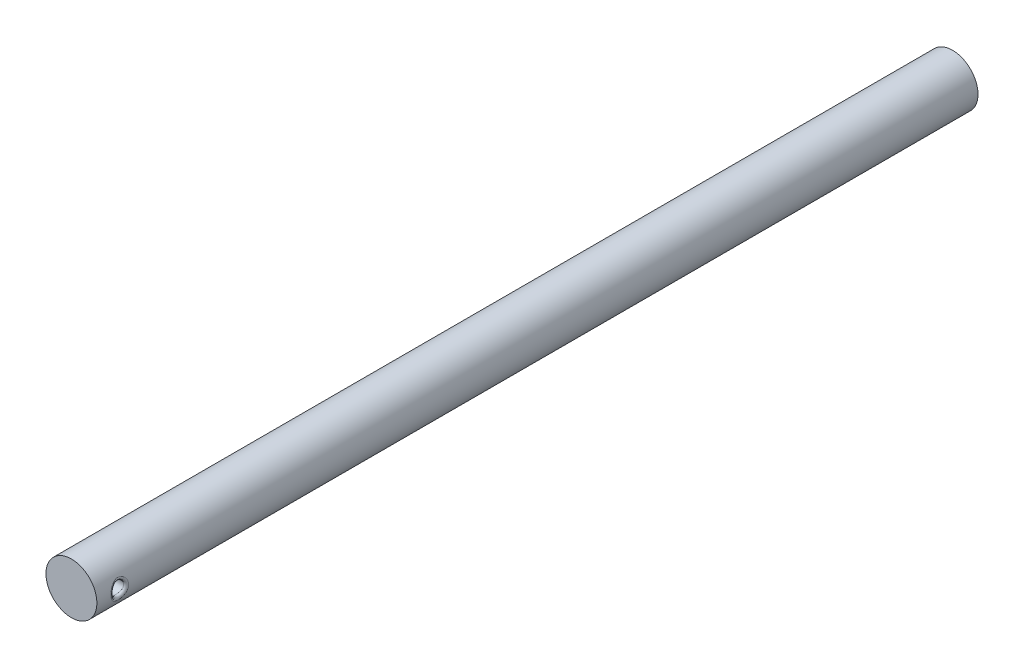
SolidWorks part; units mm, degrees
ref_plane "Alzado" through (0, 0, 0) normal (0, 0, 1) x (1, 0, 0)
ref_plane "Planta" through (0, 0, 0) normal (0, 1, 0) x (1, 0, 0)
ref_plane "Vista lateral" through (0, 0, 0) normal (1, 0, 0) x (0, 0, -1)
sketch "Croquis1" plane through (0, 0, 0) normal (0, 0, 1) x (1, 0, 0)
  circle A0 centre (0, 0) radius 10
  dimension "D1" = 20
extrude "Saliente-Extruir1" add sketch "Croquis1" along normal blind 346
sketch "Croquis2" plane through (0, 0, 0) normal (1, 0, 0) x (0, 0, -1)
  line L0 (-346, 0) -> (-337, 0) construction
  line L1 (-346, 10) -> (-346, -10) construction
  circle A0 centre (-337, 0) radius 2.5
  dimension "D2" = 5
  dimension "D1" = 9
extrude "Cortar-Extruir1" cut sketch "Croquis2" against normal through all both and the other way through all
fillet "Redondeo1" radius 1 2 edges at (-9.988, -0.489, 339.4517) (9.988, 0.489, 339.4517)
